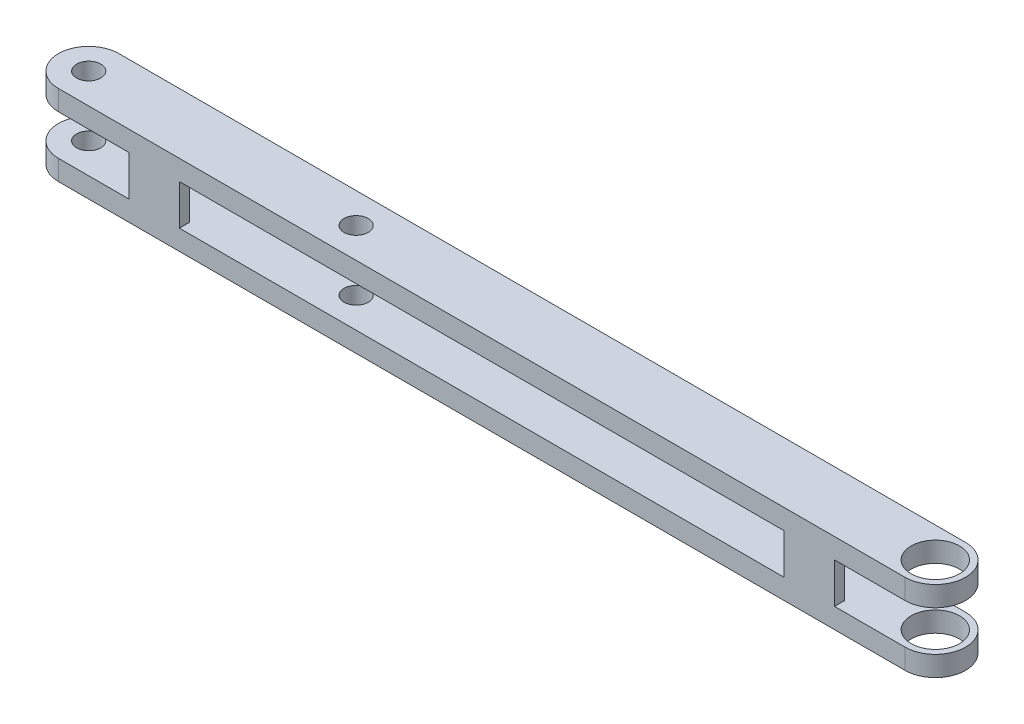
SolidWorks part; units mm, degrees
ref_plane "前视基准面" through (0, 0, 0) normal (0, 0, 1) x (1, 0, 0)
ref_plane "上视基准面" through (0, 0, 0) normal (0, 1, 0) x (1, 0, 0)
ref_plane "右视基准面" through (0, 0, 0) normal (1, 0, 0) x (0, 0, -1)
sketch "草图1" plane through (0, 0, 0) normal (0, 1, 0) x (1, 0, 0)
  line L0 (-105, 0) -> (105, 0) construction
  line L1 (-105, 7.5) -> (105, 7.5)
  line L2 (-105, -7.5) -> (105, -7.5)
  arc A0 (-105, 7.5) -> (-105, -7.5) centre (-105, 0) ccw
  arc A1 (105, -7.5) -> (105, 7.5) centre (105, 0) ccw
  point P3 (0, 0)
  dimension "D1" = 210
  dimension "D2" = 15
extrude "凸台-拉伸1" add sketch "草图1" along normal blind 20
sketch "草图2" plane through (0, 0, -7.5) normal (0, 0, -1) x (-1, 0, 0)
  line L0 (0, 0) -> (0, 10) construction
  line L1 (75, 5) -> (-75, 5)
  line L2 (75, 5) -> (75, 15)
  line L3 (75, 15) -> (-75, 15)
  line L4 (-75, 5) -> (-75, 15)
  line L5 (75, 5) -> (-75, 15) construction
  line L6 (75, 15) -> (-75, 5) construction
  line L7 (-105, 0) -> (105, 0) construction
  point P0 (0, 10)
  dimension "D1" = 10
  dimension "D2" = 10
  dimension "D3" = 150
extrude "切除-拉伸3" cut sketch "草图2" against normal through all
sketch "草图3" plane through (0, 0, -7.5) normal (0, 0, -1) x (-1, 0, 0)
  line L0 (-75, 5) -> (75, 5) construction
  line L1 (112.5, 15) -> (87.5, 15)
  line L2 (112.5, 15) -> (112.5, 5)
  line L3 (112.5, 5) -> (87.5, 5)
  line L4 (87.5, 15) -> (87.5, 5)
  line L5 (75, 15) -> (-75, 15) construction
  line L6 (112.5, 0) -> (112.5, 20) construction
  line L7 (0, 0) -> (0, 43.872) construction
  line L8 (-105, 0) -> (105, 0) construction
  line L9 (-87.5, 15) -> (-87.5, 5)
  line L10 (-112.5, 5) -> (-87.5, 5)
  line L11 (-112.5, 15) -> (-112.5, 5)
  line L12 (-112.5, 15) -> (-87.5, 15)
  dimension "D1" = 25
extrude "切除-拉伸4" cut sketch "草图3" against normal through all
sketch "草图4" plane through (-87.5, 0, 0) normal (-1, 0, 0) x (0, 0, 1)
  line L0 (7.5, 5) -> (-7.5, 5) construction
  line L1 (5, 15) -> (-5, 15)
  line L2 (5, 15) -> (5, 5)
  line L3 (5, 5) -> (-5, 5)
  line L4 (-5, 15) -> (-5, 5)
  line L5 (5, 15) -> (-5, 5) construction
  line L6 (5, 5) -> (-5, 15) construction
  line L7 (0, 0) -> (0, 10) construction
  line L8 (7.5, 15) -> (-7.5, 15) construction
  point P0 (0, 10)
  dimension "D1" = 10
extrude "切除-拉伸5" cut sketch "草图4" against normal through all
sketch "草图5" plane through (0, 20, 0) normal (0, 1, 0) x (1, 0, 0)
  line L0 (-105, 0) -> (0, 0) construction
  line L1 (0, 0) -> (105, 0) construction
  circle A0 centre (-105, 0) radius 3
  circle A1 centre (105, 0) radius 6
  dimension "D1" = 6
  dimension "D2" = 12
  dimension "D3" = 105
  dimension "D4" = 105
extrude "切除-拉伸6" cut sketch "草图5" against normal through all
sketch "草图6" plane through (0, 20, 0) normal (0, 1, 0) x (1, 0, 0)
  line L0 (-38.6607, 0) -> (0, 0) construction
  circle A0 centre (-38.6607, 0) radius 3
  circle A1 centre (-98.2099, 7.3413) radius 5 construction
  dimension "D2" = 6
  dimension "D1" = 60
extrude "切除-拉伸7" cut sketch "草图6" against normal through all
